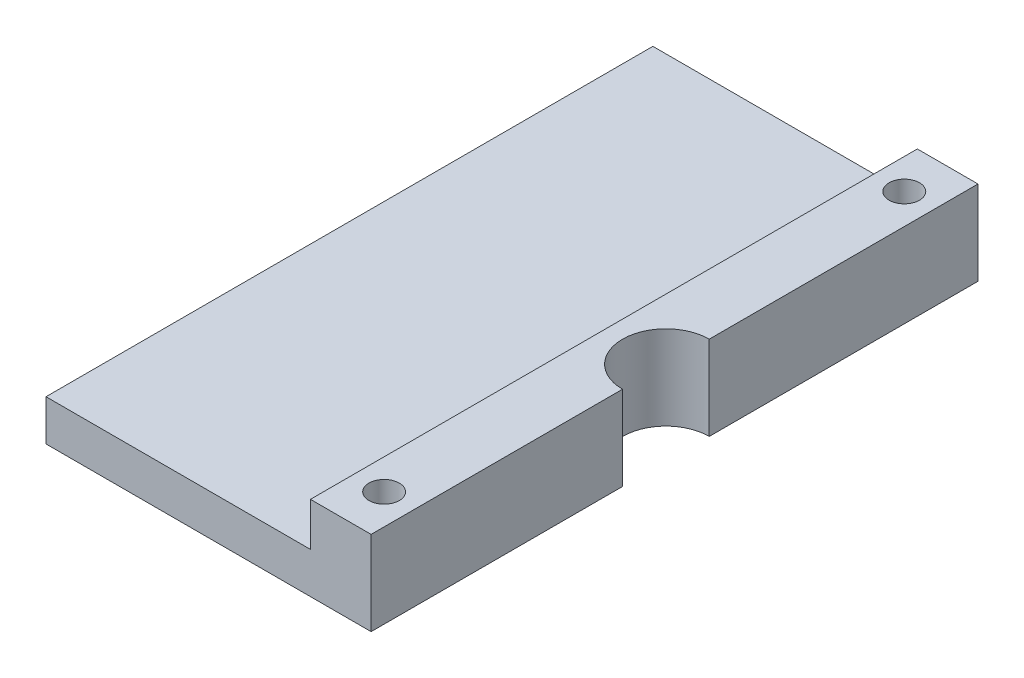
SolidWorks part; units mm, degrees
ref_plane "Front Plane" through (0, 0, 0) normal (0, 0, 1) x (1, 0, 0)
ref_plane "Top Plane" through (0, 0, 0) normal (0, 1, 0) x (1, 0, 0)
ref_plane "Right Plane" through (0, 0, 0) normal (1, 0, 0) x (0, 0, -1)
sketch "Sketch1" plane through (0, 0, 0) normal (0, 1, 0) x (1, 0, 0)
  line L1 (0, 0) -> (41.275, 0)
  line L2 (0, 0) -> (0, 88.9)
  line L3 (0, 88.9) -> (41.275, 88.9)
  line L4 (41.275, 0) -> (41.275, 88.9)
  line L5 (41.275, 88.9) -> (50.165, 88.9)
  line L6 (41.275, 88.9) -> (41.275, 0)
  line L7 (41.275, 0) -> (50.165, 0)
  line L8 (50.165, 88.9) -> (50.165, 0)
  dimension "D1" = 41.275
  dimension "D2" = 88.9
  dimension "D3" = 8.89
extrude "Boss-Extrude1" add sketch "Sketch1" along normal blind 5.9944 contours L1 L4 L3 L2 region at (20.6375, 0, -44.45)
extrude "Boss-Extrude2" add sketch "Sketch1<5>" along normal blind 12.3444 contours L8 L5 L4 L7 region at (45.72, 0, -44.45)
sketch "Sketch1<5>" plane through (0, 0, 0) normal (0, 1, 0) x (1, 0, 0) same geometry as "Sketch1"
sketch "Sketch3" plane through (0, 12.3444, 0) normal (0, 1, 0) x (1, 0, 0)
  line L0 (45.72, 82.55) -> (45.72, 6.35) construction
  line L1 (50.165, 88.9) -> (50.165, 0) construction
  line L2 (41.275, 88.9) -> (50.165, 88.9) construction
  line L3 (0, 0) -> (0, 88.9) construction
  circle A0 centre (45.72, 82.55) radius 2.2225
  circle A1 centre (45.72, 6.35) radius 2.2225
  point P4 (45.72, 44.45)
  point P6 (50.165, 44.45)
  point P7 (45.72, 88.9)
  dimension "D1" = 4.445
  dimension "D2" = 4.445
  dimension "D3" = 76.2
  dimension "D4" = 45.72
extrude "Cut-Extrude1" cut sketch "Sketch3" against normal through all both contours A1 | A0
sketch "Sketch4" plane through (0, 0, 0) normal (0, -1, 0) x (1, 0, 0)
  circle A0 centre (45.72, -6.35) radius 3.683
  circle A1 centre (45.72, -82.55) radius 3.683
  dimension "D1" = 7.366
  dimension "D2" = 7.366
extrude "Cut-Extrude2" cut sketch "Sketch4" against normal blind 4.064
sketch "Sketch5" plane through (0, 5.9944, 0) normal (0, 1, 0) x (1, 0, 0)
  line L0 (0, 0) -> (41.275, 0) construction
  line L1 (0, 88.9) -> (2.54, 88.9)
  line L2 (0, 88.9) -> (0, 0)
  line L3 (0, 0) -> (2.54, 0)
  line L4 (2.54, 88.9) -> (2.54, 0)
  dimension "D1" = 2.54
extrude "Cut-Extrude3" cut sketch "Sketch5" against normal through all both
sketch "Sketch6" plane through (0, 12.3444, 0) normal (0, 1, 0) x (1, 0, 0)
  line L1 (41.275, 0) -> (50.165, 0) construction
  line L2 (50.165, 88.9) -> (50.165, 0) construction
  circle A0 centre (50.165, 43.18) radius 6.35
  point P2 (0, 0)
  point P6 (51.7302, 43.3793)
  dimension "D1" = 12.7
  dimension "D2" = 43.18
extrude "Cut-Extrude4" cut sketch "Sketch6" against normal through all both and the other way through all
